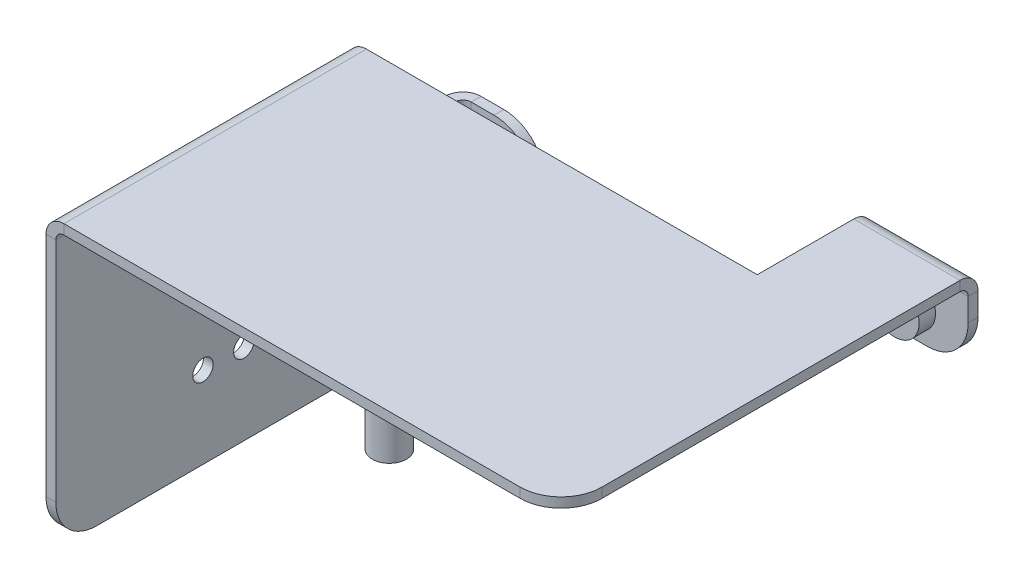
SolidWorks part; units mm, degrees
note: The reader was unsure of these and kept them because the rebuilt part matched: flange length of "边线-法兰1", "边线-法兰4", "边线-法兰5".
material "普通碳钢"
ref_plane "前视基准面" through (0, 0, 0) normal (0, 0, 1) x (1, 0, 0)
ref_plane "上视基准面" through (0, 0, 0) normal (0, 1, 0) x (1, 0, 0)
ref_plane "右视基准面" through (0, 0, 0) normal (1, 0, 0) x (0, 0, -1)
sketch "草图1" plane through (0, 0, 0) normal (0, 1, 0) x (1, 0, 0)
  line L0 (-83.8627, 0) -> (110.4127, 0) construction
  line L1 (0, 63.7204) -> (0, -53.6228) construction
  line L2 (18.5, 24.606) -> (31.5, 24.606)
  line L3 (31.5, 24.606) -> (31.5, -21.394)
  line L4 (26.5, -26.394) -> (-31.5, -26.394)
  line L5 (-31.5, -26.394) -> (-31.5, 10.606)
  line L6 (-31.5, 10.606) -> (18.5, 10.606)
  line L7 (18.5, 10.606) -> (18.5, 24.606)
  arc A0 (31.5, -21.394) -> (26.5, -26.394) centre (26.5, -21.394) cw
  dimension "D5" = 5
  dimension "D1" = 51
  dimension "D2" = 63
  dimension "D3" = 50
  dimension "D4" = 14
base flange "基体-法兰1" sketch "草图1" thickness 1.2 reverse thickness direction no parameters "D1"=1
sketch "草图9" plane through (0, -1.2, 0) normal (0, -1, 0) x (1, 0, 0)
  line L0 (-31.5, -10.606) -> (-31.5, 26.394) construction
  line L1 (-31.5, 26.394) -> (26.5, 26.394) construction
  circle A0 centre (-25.5, -1.606) radius 2.1
  circle A1 centre (6.5, 22.394) radius 2.1
  circle A2 centre (6.5, -1.606) radius 2.1
  dimension "D5" = 4.2
  dimension "D1" = 32
  dimension "D2" = 24
  dimension "D3" = 6
  dimension "D4" = 4
extrude "凸台-拉伸1" add sketch "草图9" along normal blind 6.8
hole_wizard "M3 螺纹孔1" positions "草图10" profile "草图11" tap size "M3" standard "GB"
sketch "草图10" plane through (0, -8, 0) normal (0, -1, 0) x (-1, 0, 0)
  point P0 (-6.5, 1.606)
  point P3 (25.5, 1.606)
  point P6 (-6.5, -22.394)
sketch "草图11" plane through (6.5, -8, -1.606) normal (1, 0, 0) x (0, 0, -1)
  line L0 (0, 0) -> (0, 3)
  line L1 (0, 3) -> (1.25, 3)
  line L2 (1.25, 3) -> (1.25, 0)
  line L5 (1.25, 0) -> (0, 0)
  line L10 (0, 3) -> (-1.25, 3) construction
  line L11 (0, -6.35) -> (0, 107.95) construction
  dimension "螺纹孔钻头直径" = 2.5
  dimension "螺纹孔钻头深度" = 3
  dimension "导头角度" = 180
cosmetic thread "孔螺蚊线1"
cosmetic thread "孔螺蚊线2"
cosmetic thread "孔螺蚊线3"
edge flange "边线-法兰1" sketch "草图14" flange angle 90 flange length 10 flange position material inside bend radius 1 thickness 1.2 relief rectangular parameters "D6"=10
sketch "草图14" plane through (0, -1.2, -24.606) normal (0, 0, -1) x (1, 0, 0)
  line L0 (31.5, 0) -> (18.5, 0) construction
  line L1 (31.5, 0) -> (18.5, 0)
  line L2 (18.5, 0) -> (18.5, 3.8)
  line L3 (23.5, 8.8) -> (26.5, 8.8)
  line L4 (31.5, 3.8) -> (31.5, 0)
  line L5 (31.5, -1.2) -> (18.5, -1.2) construction
  arc A0 (26.5, 8.8) -> (31.5, 3.8) centre (26.5, 3.8) cw
  arc A1 (18.5, 3.8) -> (23.5, 8.8) centre (23.5, 3.8) cw
  dimension "D2" = 5
  dimension "D1" = 10
bend "边线折弯1" bend radius 1 bend angle 90 parameters "D5"=1
sketch "草图15" plane through (0, 0, -23.406) normal (0, 0, 1) x (1, 0, 0)
  line L0 (26.5, -10) -> (23.5, -10) construction
  line L1 (31.5, -2.2) -> (31.5, -5) construction
  circle A0 centre (24.5, -6) radius 3
  dimension "D1" = 6
  dimension "D2" = 4
  dimension "D3" = 7
extrude "凸台-拉伸2" add sketch "草图15" along normal blind 2
hole_wizard "M3 螺纹孔2" positions "草图16" profile "草图17" tap size "M3" standard "GB" end condition up to next
sketch "草图16" plane through (0, 0, -21.406) normal (0, 0, 1) x (1, 0, 0)
  point P0 (24.5, -6)
sketch "草图17" plane through (24.5, -6, -21.406) normal (1, 0, 0) x (0, -1, 0)
  line L0 (0, 0) -> (0, 3.2)
  line L1 (0, 3.2) -> (1.25, 3.2)
  line L2 (1.25, 3.2) -> (1.25, 0)
  line L5 (1.25, 0) -> (0, 0)
  line L11 (0, -6.35) -> (0, 107.95) construction
  dimension "通孔螺纹孔钻头直径" = 2.5
  dimension "通孔螺纹孔钻头深度" = 3.2
cosmetic thread "孔螺蚊线4"
edge flange "边线-法兰4" sketch "草图22" flange angle 90 flange length 35 flange position material inside bend radius 1 thickness 1.2 relief rectangular parameters "D6"=10
sketch "草图22" plane through (-31.5, -1.2, 0) normal (-1, 0, 0) x (0, 0, -1)
  line L2 (-26.394, 0) -> (-26.394, 28.8)
  line L3 (-21.394, 33.8) -> (24.606, 33.8)
  line L4 (24.606, 33.8) -> (24.606, 10.8)
  line L6 (24.606, 10.8) -> (10.606, 10.8)
  line L7 (10.606, 10.8) -> (10.606, 0)
  line L8 (10.606, 0) -> (-26.394, 0)
  line L9 (10.606, -1.2) -> (-26.394, -1.2) construction
  arc A0 (-21.394, 33.8) -> (-26.394, 28.8) centre (-21.394, 28.8) ccw
  dimension "D3" = 5
  dimension "D1" = 51
  dimension "D2" = 23
  dimension "D4" = 35
bend "边线折弯4" bend radius 1 bend angle 90 parameters "D5"=2
edge flange "边线-法兰5" sketch "草图25" flange angle 90 flange length 10 flange position material inside bend radius 1 thickness 1.2 relief rectangular parameters "D6"=10
sketch "草图25" plane through (-30.3, 0, -24.606) normal (0, 0, -1) x (0, 1, 0)
  line L0 (-12, 0) -> (-35, 0) construction
  line L1 (-12, 0) -> (-35, 0)
  line L2 (-35, 0) -> (-35, 3.8)
  line L3 (-30, 8.8) -> (-17, 8.8)
  line L4 (-12, 3.8) -> (-12, 0)
  line L5 (-12, -1.2) -> (-35, -1.2) construction
  arc A0 (-12, 3.8) -> (-17, 8.8) centre (-17, 3.8) ccw
  arc A1 (-30, 8.8) -> (-35, 3.8) centre (-30, 3.8) ccw
  dimension "D2" = 5
  dimension "D1" = 10
bend "边线折弯5" bend radius 1 bend angle 90 parameters "D5"=3
sketch "草图26" plane through (0, 0, -23.406) normal (0, 0, 1) x (1, 0, 0)
  line L0 (-21.5, -17) -> (-21.5, -30) construction
  line L2 (-26.5, -35) -> (-29.3, -35) construction
  circle A0 centre (-25.5, -25) radius 3
  dimension "D1" = 6
  dimension "D2" = 4
  dimension "D3" = 10
extrude "凸台-拉伸3" add sketch "草图26" along normal blind 2
hole_wizard "M3 螺纹孔3" positions "草图27" profile "草图28" tap size "M3" standard "GB" end condition up to next
sketch "草图27" plane through (0, 0, -21.406) normal (0, 0, 1) x (1, 0, 0)
  point P0 (-25.5, -25)
sketch "草图28" plane through (-25.5, -25, -21.406) normal (1, 0, 0) x (0, -1, 0)
  line L0 (0, 0) -> (0, 3.2)
  line L1 (0, 3.2) -> (1.25, 3.2)
  line L2 (1.25, 3.2) -> (1.25, 0)
  line L5 (1.25, 0) -> (0, 0)
  line L11 (0, -6.35) -> (0, 107.95) construction
  dimension "通孔螺纹孔钻头直径" = 2.5
  dimension "通孔螺纹孔钻头深度" = 3.2
cosmetic thread "孔螺蚊线5"
sketch "草图29" plane through (-31.5, 0, 0) normal (-1, 0, 0) x (0, 0, 1)
  line L0 (-22.406, -35) -> (21.394, -35) construction
  line L1 (26.394, -30) -> (26.394, -2.2) construction
  circle A0 centre (3.394, -25) radius 1.25
  circle A1 centre (8.394, -25) radius 1.25
  dimension "D1" = 2.5
  dimension "D2" = 10
  dimension "D3" = 5
  dimension "D4" = 18
extrude "切除-拉伸1" cut sketch "草图29" against normal up to next normal cut yes
sketch "折弯-线1" [suppressed] plane through (0, 0, 0) normal (0, 1, 0) x (1, 0, 0)
sketch "边界框1" [suppressed] plane through (0, 0, 0) normal (0, 1, 0) x (1, 0, 0)
sheet metal parameters "钣金6" thickness 1.2 parameters "D1"=1
flat pattern "平板型式6" [suppressed]
sketch "折弯-线2" plane through (0, 0, 0) normal (0, 1, 0) x (1, 0, 0)
sketch "边界框2" [suppressed] plane through (0, 0, 0) normal (0, 1, 0) x (1, 0, 0)
sheet metal parameters "钣金8" thickness 1.2 parameters "D1"=1
flat pattern "平板型式6"
sketch "折弯-线2" plane through (0, 0, 0) normal (0, 1, 0) x (1, 0, 0)
  line L0 (30.5566, -26.394) -> (30.5566, 24.606) construction
  line L1 (30.5566, -26.394) -> (30.5566, 24.606) construction
sketch3d "边界框2" [suppressed]
  line L0 (39.6133, 24.606, 0) -> (-31.5, 24.606, 0) construction
  line L1 (39.6133, -26.394, 0) -> (-31.5, -26.394, 0) construction
  line L2 (39.6133, 24.606, 0) -> (39.6133, -26.394, 0) construction
  line L3 (-31.5, 24.606, 0) -> (-31.5, -26.394, 0) construction
sheet metal parameters "钣金9" thickness 1.2 parameters "D1"=1
flat pattern "平板型式6"
sketch "折弯-线2" plane through (0, 0, 0) normal (0, 1, 0) x (1, 0, 0)
  line L0 (30.5566, -26.394) -> (30.5566, 24.606) construction
  line L1 (30.5566, -26.394) -> (30.5566, 24.606) construction
sketch3d "边界框2" [suppressed]
  line L0 (39.6133, 24.606, 0) -> (-31.5, 24.606, 0) construction
  line L1 (39.6133, -26.394, 0) -> (-31.5, -26.394, 0) construction
  line L2 (39.6133, 24.606, 0) -> (39.6133, -26.394, 0) construction
  line L3 (-31.5, 24.606, 0) -> (-31.5, -26.394, 0) construction
sheet metal parameters "钣金10" thickness 1.2 parameters "D1"=1
flat pattern "平板型式6" [suppressed]
sketch "折弯-线2" plane through (0, 0, 0) normal (0, 1, 0) x (1, 0, 0)
  line L0 (30.5566, -26.394) -> (30.5566, 24.606) construction
  line L1 (30.5566, -26.394) -> (30.5566, 24.606) construction
sketch3d "边界框2" [suppressed]
  line L0 (39.6133, 24.606, 0) -> (-31.5, 24.606, 0) construction
  line L1 (39.6133, -26.394, 0) -> (-31.5, -26.394, 0) construction
  line L2 (39.6133, 24.606, 0) -> (39.6133, -26.394, 0) construction
  line L3 (-31.5, 24.606, 0) -> (-31.5, -26.394, 0) construction
bend of the flat pattern "展开-<边线折弯1>1"
sheet metal parameters "钣金11" thickness 1.2 parameters "D1"=1
flat pattern "平板型式6" [suppressed]
sketch "折弯-线2" plane through (0, 0, 0) normal (0, 1, 0) x (1, 0, 0)
  line L0 (30.5566, -26.394) -> (30.5566, 24.606) construction
  line L1 (30.5566, -26.394) -> (30.5566, 24.606) construction
sketch3d "边界框2" [suppressed]
  line L0 (39.6133, 24.606, 0) -> (-31.5, 24.606, 0) construction
  line L1 (39.6133, -26.394, 0) -> (-31.5, -26.394, 0) construction
  line L2 (39.6133, 24.606, 0) -> (39.6133, -26.394, 0) construction
  line L3 (-31.5, 24.606, 0) -> (-31.5, -26.394, 0) construction
bend of the flat pattern "展开-<边线折弯1>1"
sheet metal parameters "钣金12" thickness 1.2 parameters "D1"=1
flat pattern "平板型式6" [suppressed]
sketch "折弯-线2" plane through (0, 0, 0) normal (0, 1, 0) x (1, 0, 0)
  line L0 (30.5566, -26.394) -> (30.5566, 24.606) construction
  line L1 (30.5566, -26.394) -> (30.5566, 24.606) construction
sketch3d "边界框2" [suppressed]
  line L0 (39.6133, 24.606, 0) -> (-31.5, 24.606, 0) construction
  line L1 (39.6133, -26.394, 0) -> (-31.5, -26.394, 0) construction
  line L2 (39.6133, 24.606, 0) -> (39.6133, -26.394, 0) construction
  line L3 (-31.5, 24.606, 0) -> (-31.5, -26.394, 0) construction
bend of the flat pattern "展开-<边线折弯1>1"
sheet metal parameters "钣金13" thickness 1.2 parameters "D1"=1
flat pattern "平板型式6"
sketch "折弯-线2" plane through (0, 0, 0) normal (0, 1, 0) x (1, 0, 0)
  line L2 (-30.5566, 14.606) -> (-30.5566, -26.394) construction
  line L3 (31.5, 23.6626) -> (18.5, 23.6626) construction
  line L4 (-30.5566, 14.606) -> (-30.5566, -26.394) construction
  line L5 (31.5, 23.6626) -> (18.5, 23.6626) construction
  point P0 (30.5566, -26.394)
  point P1 (30.5566, 24.606)
sketch3d "边界框2" [suppressed]
  line L0 (31.5, 32.7193, 0) -> (-63.303, 32.7193, 0) construction
  line L1 (31.5, -26.394, 0) -> (-63.303, -26.394, 0) construction
  line L2 (31.5, 32.7193, 0) -> (31.5, -26.394, 0) construction
  line L3 (-63.303, 32.7193, 0) -> (-63.303, -26.394, 0) construction
bend of the flat pattern "展开-<边线折弯1>1"
bend of the flat pattern "展开-<边线折弯4>1"
sheet metal parameters "钣金14" thickness 1.2 parameters "D1"=1
flat pattern "平板型式6"
sketch "折弯-线2" plane through (0, 0, 0) normal (0, 1, 0) x (1, 0, 0)
  line L0 (-40.303, 24.8626) -> (-63.303, 24.8626) construction
  line L1 (-40.303, 24.8626) -> (-63.303, 24.8626) construction
  line L2 (-30.5566, 14.606) -> (-30.5566, -26.394) construction
  line L3 (31.5, 23.6626) -> (18.5, 23.6626) construction
  line L4 (-30.5566, 14.606) -> (-30.5566, -26.394) construction
  line L5 (31.5, 23.6626) -> (18.5, 23.6626) construction
sketch3d "边界框2" [suppressed]
  line L0 (31.5, 38.3193, 0) -> (-63.303, 38.3193, 0) construction
  line L1 (31.5, -26.394, 0) -> (-63.303, -26.394, 0) construction
  line L2 (31.5, 38.3193, 0) -> (31.5, -26.394, 0) construction
  line L3 (-63.303, 38.3193, 0) -> (-63.303, -26.394, 0) construction
bend of the flat pattern "展开-<边线折弯1>1"
bend of the flat pattern "展开-<边线折弯4>1"
bend of the flat pattern "展开-<边线折弯5>1"
sheet metal parameters "钣金15" thickness 1.2 parameters "D1"=1
flat pattern "平板型式6"
sketch "折弯-线2" plane through (0, 0, 0) normal (0, 1, 0) x (1, 0, 0)
  line L0 (-40.303, 24.8626) -> (-63.303, 24.8626) construction
  line L1 (-40.303, 24.8626) -> (-63.303, 24.8626) construction
  line L2 (-30.5566, 14.606) -> (-30.5566, -26.394) construction
  line L3 (31.5, 23.6626) -> (18.5, 23.6626) construction
  line L4 (-30.5566, 14.606) -> (-30.5566, -26.394) construction
  line L5 (31.5, 23.6626) -> (18.5, 23.6626) construction
sketch3d "边界框2" [suppressed]
  line L0 (31.5, 38.3193, 0) -> (-63.303, 38.3193, 0) construction
  line L1 (31.5, -26.394, 0) -> (-63.303, -26.394, 0) construction
  line L2 (31.5, 38.3193, 0) -> (31.5, -26.394, 0) construction
  line L3 (-63.303, 38.3193, 0) -> (-63.303, -26.394, 0) construction
bend of the flat pattern "展开-<边线折弯1>1"
bend of the flat pattern "展开-<边线折弯4>1"
bend of the flat pattern "展开-<边线折弯5>1"
sheet metal parameters "钣金16" thickness 1.2 parameters "D1"=1
flat pattern "平板型式6"
sketch "折弯-线2" plane through (0, 0, 0) normal (0, 1, 0) x (1, 0, 0)
  line L0 (-41.6133, 23.6626) -> (-64.6133, 23.6626) construction
  line L1 (-41.6133, 23.6626) -> (-64.6133, 23.6626) construction
  line L2 (-30.5566, 10.606) -> (-30.5566, -26.394) construction
  line L3 (31.5, 23.6626) -> (18.5, 23.6626) construction
  line L4 (-30.5566, 10.606) -> (-30.5566, -26.394) construction
  line L5 (31.5, 23.6626) -> (18.5, 23.6626) construction
sketch3d "边界框2" [suppressed]
  line L0 (-91.1133, 54.1132, 0) -> (5, 54.1133, 0) construction
  line L1 (-91.1132, -5, 0) -> (5, -5, 0) construction
  line L2 (-91.1133, 54.1132, 0) -> (-91.1132, -5, 0) construction
  line L3 (5, 54.1133, 0) -> (5, -5, 0) construction
bend of the flat pattern "展开-<边线折弯1>1"
bend of the flat pattern "展开-<边线折弯4>1"
bend of the flat pattern "展开-<边线折弯5>1"
sheet metal parameters "钣金17" thickness 1.2 parameters "D1"=1
flat pattern "平板型式6"
sketch "折弯-线2" plane through (0, 0, 0) normal (0, 1, 0) x (1, 0, 0)
  line L0 (-41.6133, 23.6626) -> (-64.6133, 23.6626) construction
  line L1 (-41.6133, 23.6626) -> (-64.6133, 23.6626) construction
  line L2 (-30.5566, 10.606) -> (-30.5566, -26.394) construction
  line L3 (31.5, 23.6626) -> (18.5, 23.6626) construction
  line L4 (-30.5566, 10.606) -> (-30.5566, -26.394) construction
  line L5 (31.5, 23.6626) -> (18.5, 23.6626) construction
sketch3d "边界框2" [suppressed]
  line L0 (-91.1133, 54.1132, 0) -> (5, 54.1133, 0) construction
  line L1 (-91.1132, -5, 0) -> (5, -5, 0) construction
  line L2 (-91.1133, 54.1132, 0) -> (-91.1132, -5, 0) construction
  line L3 (5, 54.1133, 0) -> (5, -5, 0) construction
bend of the flat pattern "展开-<边线折弯1>1"
bend of the flat pattern "展开-<边线折弯4>1"
bend of the flat pattern "展开-<边线折弯5>1"
